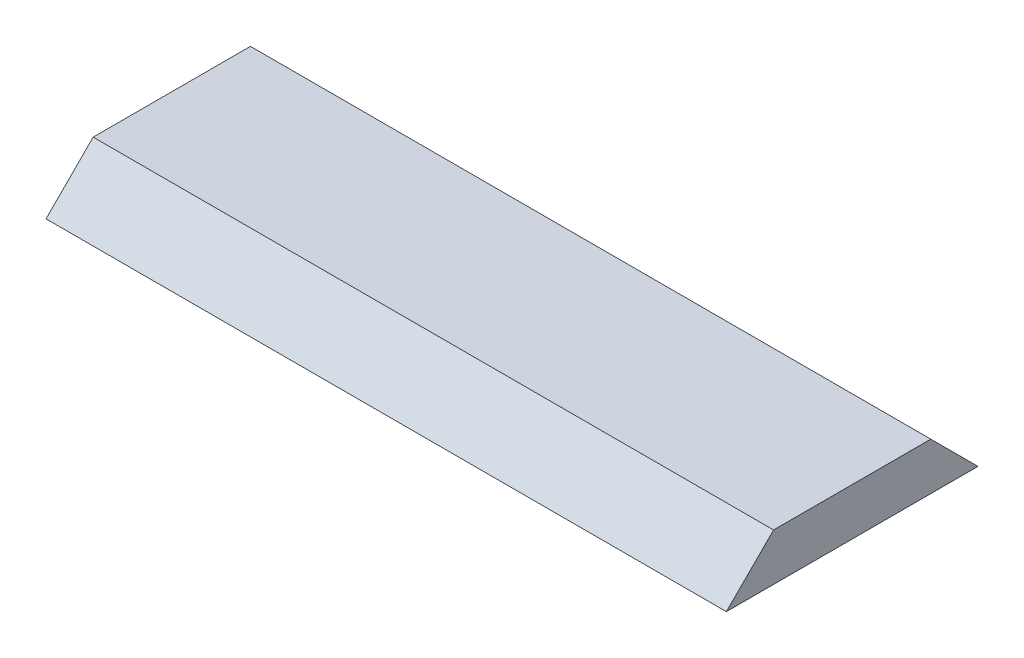
SolidWorks part; units mm, degrees
material "ABS"
ref_plane "Front Plane" through (0, 0, 0) normal (0, 0, 1) x (1, 0, 0)
ref_plane "Top Plane" through (0, 0, 0) normal (0, 1, 0) x (1, 0, 0)
ref_plane "Right Plane" through (0, 0, 0) normal (1, 0, 0) x (0, 0, -1)
sketch "Sketch1" plane through (0, 0, 0) normal (0, 1, 0) x (1, 0, 0)
  line L1 (-64.9, 25) -> (64.9, 25)
  line L2 (-64.9, 25) -> (-64.9, -25)
  line L3 (-64.9, -25) -> (64.9, -25)
  line L4 (64.9, 25) -> (64.9, -25)
  line L5 (-64.9, 25) -> (64.9, -25) construction
  line L6 (-64.9, -25) -> (64.9, 25) construction
  point P0 (0, 0)
  dimension "D1" = 129.8
  dimension "D2" = 50
extrude "Boss-Extrude1" add sketch "Sketch1" along normal blind 9
sketch "Sketch2" plane through (0, 0, 0) normal (0, -1, 0) x (1, 0, 0)
  line L0 (-64.9, 0) -> (64.9, 0) construction
  line L1 (-64.9, -25) -> (-64.9, 25) construction
  line L2 (64.9, 25) -> (64.9, -25) construction
  line L3 (-64.9, 25) -> (-64.9, 0) construction
  line L4 (-32.45, 12.5) -> (0, 12.5) construction
  line L5 (-64.9, 12.5) -> (-32.45, 12.5) construction
  line L6 (0, 12.5) -> (32.45, 12.5) construction
  line L7 (32.45, 12.5) -> (64.9, 12.5) construction
  circle A0 centre (-32.45, 12.5) radius 2.35
  circle A1 centre (0, 12.5) radius 2.35
  circle A2 centre (32.45, 12.5) radius 2.35
  circle A3 centre (32.45, -12.5) radius 2.35
  circle A4 centre (0, -12.5) radius 2.35
  circle A5 centre (-32.45, -12.5) radius 2.35
  dimension "D1" = 4.7
  dimension "D2" = 4.7
  dimension "D3" = 4.7
extrude "Cut-Extrude1" cut sketch "Sketch2" against normal blind 8
chamfer "Chamfer1" distance 1 angle 45 6 edges at (-32.45, 0, -10.15) (0, 0, -10.15) (32.45, 0, -10.15) (32.45, 0, 10.15) (0, 0, 10.15) (-32.45, 0, 10.15)
chamfer "Chamfer2" distance 10 angle 45 2 edges at (0, 9, 25) (0, 9, -25)
